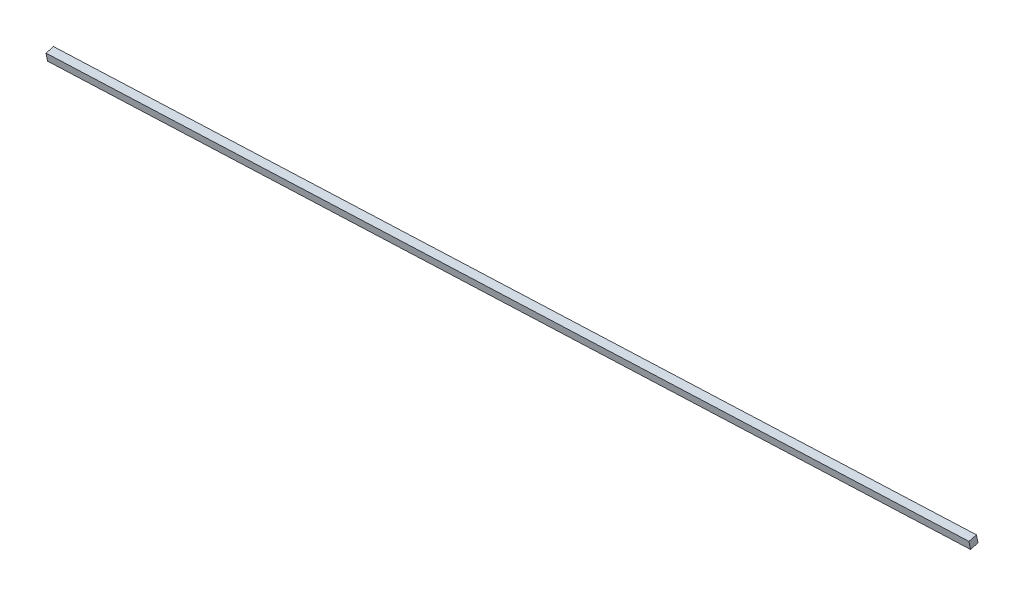
SolidWorks part; units mm, degrees
material "Thornel VCB-20 Carbon Cloth"
ref_plane "Front Plane" through (0, 0, 0) normal (0, 0, 1) x (1, 0, 0)
ref_plane "Top Plane" through (0, 0, 0) normal (0, 1, 0) x (1, 0, 0)
ref_plane "Right Plane" through (0, 0, 0) normal (1, 0, 0) x (0, 0, -1)
ref_plane "Plane1" through (-62.4144, 0, 2.7251) normal (-0.999, 0, 0.0436) x (0.0436, 0, 0.999)
ref_plane "Plane2" through (-39.4363, 0, 1.7218) normal (-0.999, 0, 0.0436) x (0.0436, 0, 0.999)
ref_plane "Plane3" through (-371.6426, 0, 16.2263) normal (-0.999, 0, 0.0436) x (0.0436, 0, 0.999)
sketch "Sketch2" plane through (-39.4363, 0, 1.7218) normal (-0.999, 0, 0.0436) x (0.0436, 0, 0.999)
  line L4 (7.0684, 27.2821) -> (6.6504, 25.2752)
  line L5 (7.038, 24.6838) -> (9.0449, 24.2657)
  line L6 (9.6363, 24.6533) -> (10.0544, 26.6602)
  line L7 (9.6668, 27.2517) -> (7.6599, 27.6697)
  line L8 (7.0684, 27.2821) -> (6.6504, 25.2752)
  line L9 (7.038, 24.6838) -> (9.0449, 24.2657)
  line L10 (9.6363, 24.6533) -> (10.0544, 26.6602)
  line L11 (9.6668, 27.2517) -> (7.6599, 27.6697)
  arc A8 (6.6504, 25.2752) -> (7.038, 24.6838) centre (6.5485, 24.7857) ccw
  arc A9 (6.6504, 25.2752) -> (7.038, 24.6838) centre (6.5485, 24.7857) ccw
  arc A10 (9.0449, 24.2657) -> (9.6363, 24.6533) centre (9.5344, 24.1638) ccw
  arc A11 (9.0449, 24.2657) -> (9.6363, 24.6533) centre (9.5344, 24.1638) ccw
  arc A12 (10.0544, 26.6602) -> (9.6668, 27.2517) centre (10.1563, 27.1497) ccw
  arc A13 (10.0544, 26.6602) -> (9.6668, 27.2517) centre (10.1563, 27.1497) ccw
  arc A14 (7.6599, 27.6697) -> (7.0684, 27.2821) centre (7.1704, 27.7716) ccw
  arc A15 (7.6599, 27.6697) -> (7.0684, 27.2821) centre (7.1704, 27.7716) ccw
  dimension "D1" = 0
sketch "Sketch3" plane through (-39.4363, 0, 1.7218) normal (-0.999, 0, 0.0436) x (0.0436, 0, 0.999)
  line L5 (8.6634, 27.4607) -> (8.0414, 24.4748) construction
  line L6 (6.578, 24.8051) -> (7.1898, 27.7421)
  line L7 (6.578, 24.8051) -> (9.515, 24.1934)
  line L12 (7.1898, 27.7421) -> (10.1267, 27.1303)
  line L13 (7.0684, 27.2821) -> (6.6504, 25.2752)
  line L14 (7.038, 24.6838) -> (9.0449, 24.2657)
  line L15 (9.6363, 24.6533) -> (10.0544, 26.6602)
  line L16 (9.6668, 27.2517) -> (7.6599, 27.6697)
  line L17 (7.0684, 27.2821) -> (6.6504, 25.2752)
  line L18 (7.038, 24.6838) -> (9.0449, 24.2657)
  line L19 (9.6363, 24.6533) -> (10.0544, 26.6602)
  line L20 (9.6668, 27.2517) -> (7.6599, 27.6697)
  line L21 (9.515, 24.1934) -> (10.1267, 27.1303)
  line L22 (6.578, 24.8051) -> (10.1267, 27.1303) construction
  line L23 (7.1898, 27.7421) -> (9.515, 24.1934) construction
  arc A12 (6.6504, 25.2752) -> (7.038, 24.6838) centre (6.5485, 24.7857) ccw
  arc A13 (9.0449, 24.2657) -> (9.6363, 24.6533) centre (9.5344, 24.1638) ccw
  arc A14 (10.0544, 26.6602) -> (9.6668, 27.2517) centre (10.1563, 27.1497) ccw
  arc A15 (7.6599, 27.6697) -> (7.0684, 27.2821) centre (7.1704, 27.7716) ccw
  arc A16 (6.6504, 25.2752) -> (7.038, 24.6838) centre (6.5485, 24.7857) ccw
  arc A17 (9.0449, 24.2657) -> (9.6363, 24.6533) centre (9.5344, 24.1638) ccw
  arc A18 (10.0544, 26.6602) -> (9.6668, 27.2517) centre (10.1563, 27.1497) ccw
  arc A19 (7.6599, 27.6697) -> (7.0684, 27.2821) centre (7.1704, 27.7716) ccw
  point P13 (8.3524, 25.9677)
  dimension "D2" = 3
  dimension "D3" = 3
  dimension "D1" = 0
extrude "Boss-Extrude1" add sketch "Sketch3" along normal up to surface (332.5228 mm away) contours L6 L7 L21 L12 up to plane "Plane3"
